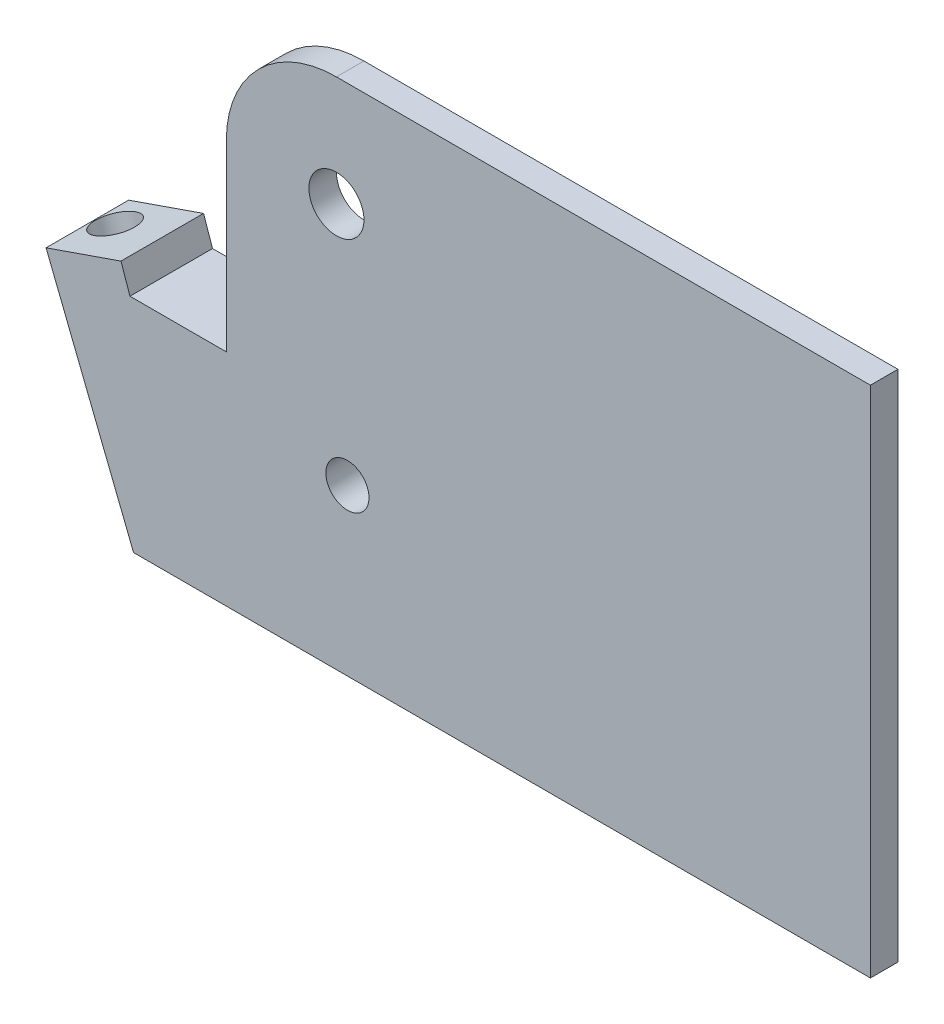
SolidWorks part; units mm, degrees
ref_plane "Front Plane" through (0, 0, 0) normal (0, 0, 1) x (1, 0, 0)
ref_plane "Top Plane" through (0, 0, 0) normal (0, 1, 0) x (1, 0, 0)
ref_plane "Right Plane" through (0, 0, 0) normal (1, 0, 0) x (0, 0, -1)
sketch "Sketch2" plane through (0, 0, 0) normal (0, 0, 1) x (1, 0, 0)
  line L0 (-36.2055, -212.6584) -> (-69.6869, -224.2524) construction
  line L1 (-60.011, -224.2524) -> (-48.895, -224.2524)
  line L4 (25.4, -305.6274) -> (25.4, 320.675) construction
  line L5 (25.4, -224.2524) -> (25.4, -249.6524)
  line L6 (25.4, -249.6524) -> (-59.5964, -249.6524)
  line L7 (-59.5964, -249.6524) -> (-69.6869, -224.2524)
  line L8 (-48.895, -224.2524) -> (-48.895, -203.1334)
  line L10 (-36.195, -190.4334) -> (25.4, -190.4334)
  line L11 (25.4, -190.4334) -> (25.4, -224.2524)
  line L13 (-69.6869, -224.2524) -> (-61.047, -221.2606)
  line L14 (-61.047, -221.2606) -> (-60.011, -224.2524)
  circle A0 centre (-36.195, -203.1334) radius 3.175
  circle A1 centre (-36.195, -203.1334) radius 39.5944 construction
  arc A2 (-74.6371, -212.6159) -> (-69.6869, -224.2524) centre (-36.195, -203.1334) ccw construction
  arc A4 (-36.195, -190.4334) -> (-48.895, -203.1334) centre (-36.195, -203.1334) ccw
  dimension "D1" = 12.7
extrude "Boss-Extrude1" add sketch "Sketch2" along normal blind 3.175
sketch "Sketch3" plane through (0, 0, 0) normal (0, 0, -1) x (-1, 0, 0)
  line L0 (69.6869, -224.2524) -> (59.5964, -249.6524)
  line L1 (59.5964, -249.6524) -> (25.4, -249.6524)
  line L2 (25.4, -320.675) -> (25.4, 320.675) construction
  line L3 (59.5964, -249.6524) -> (-25.4, -249.6524) construction
  line L4 (25.4, -249.6524) -> (25.4, -224.2524)
  line L6 (25.4, -224.2524) -> (60.011, -224.2524)
  line L7 (60.011, -224.2524) -> (61.047, -221.2606)
  line L8 (61.047, -221.2606) -> (69.6869, -224.2524)
extrude "Boss-Extrude2" add sketch "Sketch3" along normal blind 6.35
sketch "Sketch4" plane through (61.8785, -178.6935, 0) normal (-0.3272, 0.9449, 0) x (0.9449, 0.3272, 0)
  line L1 (-95.8313, 4.7625) -> (-140.1004, 4.7625) construction
  line L2 (-136.6903, 4.7625) -> (-136.6903, 2.3812) construction
  line L3 (-136.6903, 4.7625) -> (-139.2303, 4.7625) construction
  line L4 (-139.2303, -3.175) -> (-139.2303, 6.35) construction
  dimension "D1" = 2.54
hole_wizard "3/16 (0.1875) Diameter Hole1" positions "Sketch9" profile "Sketch10" hole size "3/16" standard "ANSI Inch"
sketch "Sketch9" plane through (61.8785, -178.6935, 0) normal (-0.3272, 0.9449, 0) x (0.9449, 0.3272, 0)
  point P0 (-136.6903, 2.3812)
sketch "Sketch10" plane through (-67.2867, -223.4212, -2.3812) normal (0, 0, 1) x (-0.9449, -0.3272, 0)
  line L0 (0, 0) -> (0, 3.9708)
  line L1 (0, 3.9708) -> (2.3812, 2.54)
  line L2 (2.3812, 2.54) -> (2.3812, 0)
  line L5 (2.3812, 0) -> (0, 0)
  line L10 (0, 3.9708) -> (-2.3812, 2.54) construction
  line L11 (0, -6.35) -> (0, 107.95) construction
  dimension "Hole Dia." = 4.7625
  dimension "Hole Depth" = 2.54
  dimension "Drill Angle" = 118
sketch "Sketch11" plane through (0, 0, -6.35) normal (0, 0, -1) x (-1, 0, 0)
  line L0 (25.4, -224.2524) -> (34.925, -224.2524) construction
  line L1 (60.011, -224.2524) -> (25.4, -224.2524) construction
  line L2 (34.925, -224.2524) -> (34.925, -230.6024) construction
  dimension "D1" = 9.525
hole_wizard "#10 Clearance Hole1" positions "Sketch12" profile "Sketch13" hole size "#10" standard "ANSI Inch" end condition through all
sketch "Sketch12" plane through (0, 0, -6.35) normal (0, 0, -1) x (-1, 0, 0)
  point P0 (34.925, -230.6024)
sketch "Sketch13" plane through (-34.925, -230.6024, -6.35) normal (1, 0, 0) x (0, 1, 0)
  line L0 (0, 0) -> (0, 9.525)
  line L1 (0, 9.525) -> (2.4892, 9.525)
  line L2 (2.4892, 9.525) -> (2.4892, 0)
  line L5 (2.4892, 0) -> (0, 0)
  line L11 (0, -6.35) -> (0, 107.95) construction
  dimension "Thru Hole Dia." = 4.9784
  dimension "Thru Hole Depth" = 9.525
